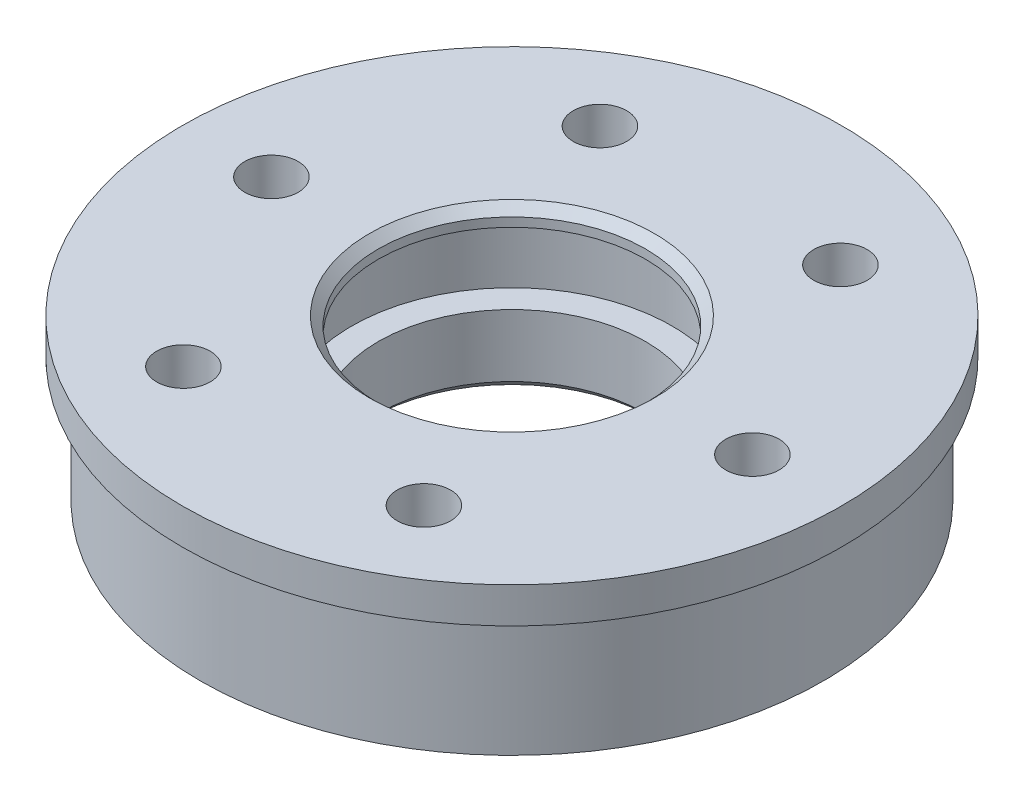
SolidWorks part; units mm, degrees
ref_plane "Front Plane" through (0, 0, 0) normal (0, 0, 1) x (1, 0, 0)
ref_plane "Top Plane" through (0, 0, 0) normal (0, 1, 0) x (1, 0, 0)
ref_plane "Right Plane" through (0, 0, 0) normal (1, 0, 0) x (0, 0, -1)
sketch "Sketch1" plane through (0, 0, 0) normal (0, 1, 0) x (1, 0, 0)
  circle A0 centre (0, 0) radius 13.5 construction
  circle A1 centre (13.5, 0) radius 1.5
  circle A2 centre (6.75, -11.6913) radius 1.5
  circle A3 centre (-6.75, -11.6913) radius 1.5
  circle A4 centre (-13.5, 0) radius 1.5
  circle A5 centre (-6.75, 11.6913) radius 1.5
  circle A6 centre (6.75, 11.6913) radius 1.5
  circle A7 centre (0, 0) radius 17.5
  circle A8 centre (0, 0) radius 7.5
  point P17 (0, 0)
  dimension "D1" = 27
  dimension "D2" = 3
  dimension "D4" = 35
  dimension "D5" = 15
  dimension "D3" = 6
extrude "Boss-Extrude1" add sketch "Sketch1" along normal mid plane 9
sketch "Sketch2" plane through (0, 0, 0) normal (0, 1, 0) x (1, 0, 0)
  circle A0 centre (0, 0) radius 9
  dimension "D1" = 18
extrude "Cut-Extrude1" cut sketch "Sketch2" along normal blind 4 from offset 0.5 offset against normal yes
sketch "Sketch3" plane through (0, -4.5, 0) normal (0, -1, 0) x (1, 0, 0)
  circle A0 centre (0, 0) radius 12
  circle A1 centre (0, 0) radius 15
  circle A2 centre (-13.5, 0) radius 1.5 construction
extrude "Boss-Extrude2" add sketch "Sketch3" against normal blind 1.5
chamfer "Chamfer1" distance 0.5 angle 45 2 edges at (0, -4.5, 7.5) (0, 4.5, 7.5)
sketch "Sketch4" plane through (0, 4.5, 0) normal (0, 1, 0) x (1, 0, 0)
  circle A0 centre (0, 0) radius 18.5
  circle A1 centre (0, 0) radius 17.5 construction
  circle A2 centre (0, 0) radius 17.5
  dimension "D1" = 1
extrude "Boss-Extrude3" add sketch "Sketch4" against normal blind 2
sketch "Sketch5" plane through (0, -4.5, 0) normal (0, -1, 0) x (-1, 0, 0)
  line L0 (0, 0) -> (-10.8253, -6.25) construction
  line L1 (0, 0) -> (-12.5, 0) construction
  circle A0 centre (0, 0) radius 12.5 construction
  circle A1 centre (-10.8253, -6.25) radius 2.35
  circle A2 centre (-10.8253, 6.25) radius 2.35
  circle A3 centre (0, 12.5) radius 2.35
  circle A4 centre (10.8253, 6.25) radius 2.35
  circle A5 centre (10.8253, -6.25) radius 2.35
  circle A6 centre (0, -12.5) radius 2.35
  point P18 (0, 0)
  dimension "D1" = 4.7
  dimension "D2" = 25
  dimension "D3" = 30
  dimension "D4" = 6
extrude "Cut-Extrude2" cut sketch "Sketch5" against normal blind 4
chamfer "Chamfer2" [suppressed] distance 3 angle 45
equation "\"D5@Sketch1\"=18-3"
